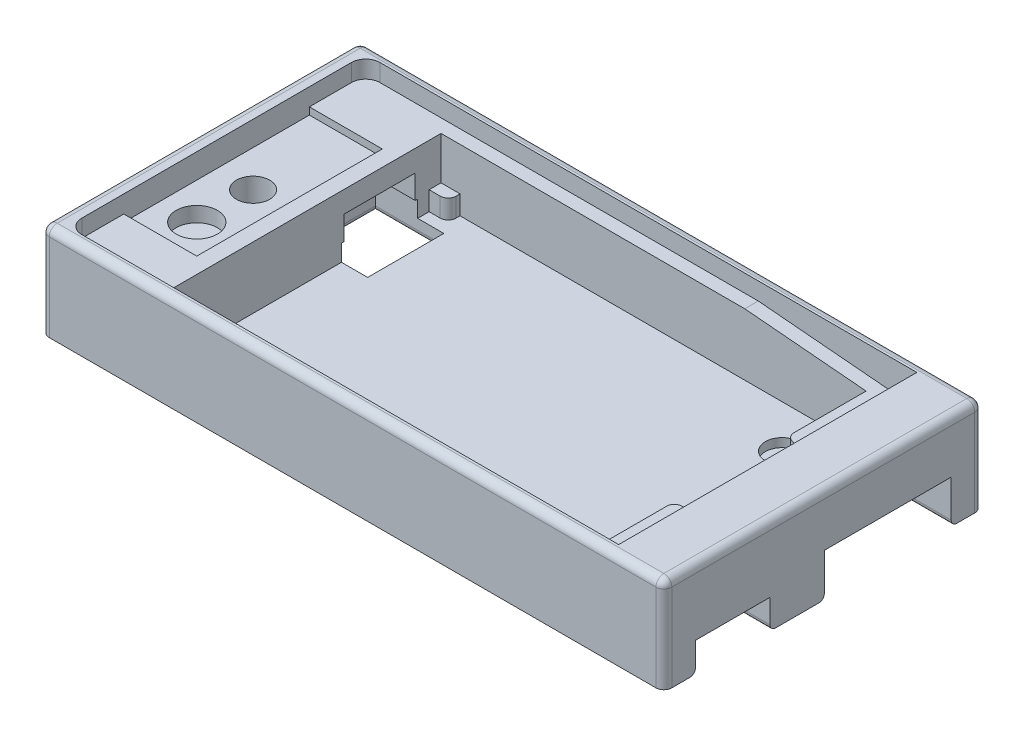
SolidWorks part; units mm, degrees
ref_plane "前视基准面" through (0, 0, 0) normal (0, 0, 1) x (1, 0, 0)
ref_plane "上视基准面" through (0, 0, 0) normal (0, 1, 0) x (1, 0, 0)
ref_plane "右视基准面" through (0, 0, 0) normal (1, 0, 0) x (0, 0, -1)
other "Configuration Table"
sketch "草图1" plane through (0, 0, 0) normal (0, 1, 0) x (1, 0, 0)
  line L0 (-39.25, 0) -> (39.25, 0) construction
  line L1 (-39.25, 20.1) -> (39.25, 20.1)
  line L2 (-39.25, 20.1) -> (-39.25, -20.1)
  line L3 (-39.25, -20.1) -> (39.25, -20.1)
  line L4 (39.25, 20.1) -> (39.25, -20.1)
  line L5 (-39.25, 20.1) -> (39.25, -20.1) construction
  line L6 (-39.25, -20.1) -> (39.25, 20.1) construction
  line L7 (-26.05, -17.1) -> (27.55, -17.1)
  line L8 (-26.05, -17.1) -> (-26.05, 17.1)
  line L9 (-26.05, 17.1) -> (27.55, 17.1)
  line L10 (27.55, -17.1) -> (27.55, 17.1)
  line L12 (32.25, 6.9973) -> (34.45, 6.9973)
  line L13 (32.25, 6.9973) -> (32.25, -6.9973)
  line L14 (32.25, -6.9973) -> (34.45, -6.9973)
  line L15 (34.45, 6.9973) -> (34.45, -6.9973)
  line L16 (-37.25, 18.8) -> (32.25, 18.8)
  line L17 (-37.25, 18.8) -> (-37.25, -18.8)
  line L18 (-37.25, -18.8) -> (32.25, -18.8)
  line L19 (32.25, 18.8) -> (32.25, -18.8)
  circle A0 centre (-32.65, 7.1) radius 2.6
  circle A1 centre (-32.65, 0) radius 2.1
  circle A2 centre (22.35, 11.6973) radius 2.1
  circle A3 centre (22.35, -11.6973) radius 2.1
  circle A4 centre (-32.65, -7.1) radius 2.6
  point P0 (0, 0)
  dimension "D1" = 4.2
  dimension "D6" = 5.2
  dimension "D2" = 5.2
  dimension "D3" = 5.4027
  dimension "D4" = 6.6
  dimension "D5" = 13
  dimension "D7" = 3
  dimension "D8" = 3
  dimension "D9" = 6.6
  dimension "D10" = 11.7
  dimension "D11" = 53.6
  dimension "D12" = 34.2
  dimension "D13" = 2.2
  dimension "D14" = 4.7
  dimension "D15" = 1.3
  dimension "D16" = 1.3
  dimension "D17" = 2
  dimension "D18" = 7
extrude "凸台-拉伸2" add sketch "草图1" along normal blind 2.2 contours L4 L1 L2 L3 L16 L19 L10 L12 L15 L14 L18 L17 | L15 L12 L10 L14 region at (0, 0, -19.2181) region at (33.35, 0, 0)
extrude "凸台-拉伸3" add sketch "草图1<4>" against normal blind 7.8 contours L19 L16 L17 L18 L7 L8 L9 A0 A1 A4 | L4 L1 L2 L3 L16 L19 L10 L12 L15 L14 L18 L17 | A4 | A0 | A1 | L15 L12 L13 L14 region at (0, 0, -19.2181) region at (33.35, 0, 0) region at (31.4598, 0, 0) region at (-32.65, 0, -7.1) region at (-32.65, 0, 0) region at (-32.65, 0, 7.1)
sketch "草图1<4>" plane through (0, 0, 0) normal (0, 1, 0) x (1, 0, 0) same geometry as "草图1"
sketch "草图2" plane through (0, 0, 0) normal (0, 1, 0) x (1, 0, 0)
  line L0 (-37.25, 18.8) -> (-37.25, -18.8) construction
  line L1 (-37.25, 11.7) -> (-28.05, 11.7)
  line L2 (-37.25, 11.7) -> (-37.25, -11.7)
  line L3 (-37.25, -11.7) -> (-28.05, -11.7)
  line L4 (-28.05, 11.7) -> (-28.05, -11.7)
  circle A0 centre (-32.65, 7.1) radius 2.6 construction
  circle A1 centre (-32.65, 7.1) radius 2.6 construction
  circle A2 centre (-32.65, -7.1) radius 2.6 construction
  circle A3 centre (-32.65, -7.1) radius 2.6 construction
  dimension "D1" = 4.6
  dimension "D2" = 4.6
  dimension "D3" = 4.6
extrude "切除-拉伸1" cut sketch "草图2" against normal blind 0.9
sketch "草图6" plane through (0, -0.9, 0) normal (0, 1, 0) x (1, 0, 0)
  circle A0 centre (-32.65, 7.1) radius 2.6 construction
  circle A1 centre (-32.65, 7.1) radius 2.6
  circle A2 centre (-32.65, -7.1) radius 2.6 construction
  circle A3 centre (-32.65, -7.1) radius 2.6
extrude "切除-拉伸2" cut sketch "草图6" against normal blind 1.9 contours A3 region at (-32.65, -0.9, 7.1)
sketch "草图7" plane through (0, -0.9, 0) normal (0, 1, 0) x (1, 0, 0)
  circle A0 centre (-32.65, 0) radius 2.1 construction
  circle A1 centre (-32.65, 0) radius 2.1
extrude "切除-拉伸3" cut sketch "草图7" against normal blind 1.1
sketch "草图8" plane through (0, -2, 0) normal (0, 1, 0) x (1, 0, 0)
  circle A0 centre (-32.65, 0) radius 1.2
  dimension "2.2" = 2.4
extrude "切除-拉伸4" cut sketch "草图8" against normal through all
sketch "草图9" plane through (0, -7.8, 0) normal (0, -1, 0) x (1, 0, 0)
  line L0 (39.25, -20.1) -> (39.25, 20.1) construction
  line L1 (-39.25, -20.1) -> (39.25, -20.1) construction
  line L2 (-39.25, -20.1) -> (-39.25, 20.1) construction
  line L3 (-39.25, 20.1) -> (39.25, 20.1) construction
  line L4 (39.25, -20.1) -> (39.25, 20.1)
  line L5 (-39.25, -20.1) -> (39.25, -20.1)
  line L6 (-39.25, -20.1) -> (-39.25, 20.1)
  line L7 (-39.25, 20.1) -> (39.25, 20.1)
extrude "凸台-拉伸4" add sketch "草图9" along normal blind 2
sketch "草图10" plane through (0, -7.8, 0) normal (0, 1, 0) x (1, 0, 0)
  circle A0 centre (22.35, -11.6973) radius 2.1 construction
  circle A1 centre (22.35, 11.6973) radius 2.1 construction
  circle A2 centre (22.35, -11.6973) radius 2.1
  circle A3 centre (22.35, 11.6973) radius 2.1
extrude "切除-拉伸5" cut sketch "草图10" against normal blind 1.1
sketch "草图11" plane through (0, -8.9, 0) normal (0, 1, 0) x (1, 0, 0)
  circle A0 centre (22.35, 11.6973) radius 1.2
  circle A1 centre (22.35, -11.6973) radius 1.2
  dimension "D1" = 2.4
  dimension "D2" = 2.4
extrude "切除-拉伸6" cut sketch "草图11" against normal through all
sketch "草图12" plane through (0, -9.8, 0) normal (0, -1, 0) x (1, 0, 0)
  line L0 (-26.05, -17.1) -> (27.55, -17.1) construction
  line L1 (-26.05, -17.1) -> (27.55, -17.1) construction
  line L7 (-30.8239, -4.85) -> (-26.3739, -4.85)
  line L8 (-30.8239, -4.85) -> (-30.8239, -13.85)
  line L9 (-30.8239, -13.85) -> (-26.3739, -13.85)
  line L10 (-26.3739, -4.85) -> (-26.3739, -13.85)
  line L11 (-30.8239, -4.85) -> (-26.3739, -13.85) construction
  line L12 (-30.8239, -13.85) -> (-26.3739, -4.85) construction
  line L13 (-28.5989, -9.35) -> (-23.0895, -9.35) construction
  line L14 (-31.3739, -4.55) -> (-26.3739, -4.55)
  line L15 (-31.3739, -4.55) -> (-31.3739, -14.15)
  line L16 (-31.3739, -14.15) -> (-26.3739, -14.15)
  line L17 (-26.3739, -4.55) -> (-26.3739, -14.15)
  point P6 (-28.5989, -9.35)
  dimension "D1" = 7.75
  dimension "D2" = 4.45
  dimension "D3" = 9
  dimension "D4" = 9.6
  dimension "D5" = 5
extrude "切除-拉伸7" cut sketch "草图12" against normal blind 7.1 contours L10 L7 L8 L9 region at (-28.5989, -9.8, -9.35)
extrude "切除-拉伸8" cut sketch "草图12<3>" against normal offset from surface (4.1 mm away) 3 contours L17 L14 L15 L16 L9 L8 L7 region at (-30.9321, -9.8, -9.35) up to face at (-28.5989, -2.7, -9.35)
sketch "草图12<3>" plane through (0, -9.8, 0) normal (0, -1, 0) x (1, 0, 0) same geometry as "草图12"
sketch "草图13" plane through (-26.3739, 0, 0) normal (-1, 0, 0) x (0, 0, 1)
  line L4 (-4.85, -2.7) -> (-13.85, -2.7)
  line L5 (-4.85, -2.7) -> (-13.85, -2.7)
  line L9 (-13.85, -2.7) -> (-13.85, -5.7)
  line L11 (-13.85, -5.7) -> (-14.15, -5.7)
  line L12 (-14.15, -9.8) -> (-4.55, -9.8)
  line L13 (-13.85, -5.7) -> (-14.15, -5.7)
  line L14 (-14.15, -5.7) -> (-14.15, -9.8)
  line L15 (-4.85, -5.7) -> (-4.85, -2.7)
  line L17 (-13.85, -2.7) -> (-13.85, -5.7)
  line L20 (-14.15, -9.8) -> (-4.55, -9.8)
  line L23 (-4.85, -5.7) -> (-4.85, -2.7)
  line L24 (-14.15, -5.7) -> (-14.15, -9.8)
  line L25 (-4.55, -9.8) -> (-4.55, -5.7)
  line L26 (-4.55, -9.8) -> (-4.55, -5.7)
  line L27 (-4.55, -5.7) -> (-4.85, -5.7)
  line L28 (-4.55, -5.7) -> (-4.85, -5.7)
  dimension "D1" = 0
extrude "切除-拉伸9" cut sketch "草图13" against normal up to surface (0.3239 mm away) up to face at (-26.05, -3.9, 0)
sketch "草图14" plane through (-26.05, 0, 0) normal (-1, 0, 0) x (0, 0, 1)
  line L4 (-14.15, -7.8) -> (-14.15, -9.8)
  line L5 (-14.15, -9.8) -> (-4.55, -9.8)
  line L7 (-4.55, -7.8) -> (-14.15, -7.8)
  line L9 (-14.15, -9.8) -> (-4.55, -9.8)
  line L11 (-4.55, -7.8) -> (-14.15, -7.8)
  line L12 (-14.15, -7.8) -> (-14.15, -9.8)
  line L14 (-4.55, -9.8) -> (-4.55, -7.8)
  line L15 (-4.55, -9.8) -> (-4.55, -7.8)
  dimension "D1" = 0
extrude "切除-拉伸10" cut sketch "草图14" against normal blind 3.3
fillet "圆角1" radius 1.8 4 edges at (32.25, 1.1, 18.8) (32.25, 1.1, -18.8) (-37.25, 1.1, -18.8) (-37.25, 1.1, 18.8)
fillet "圆角2" radius 1 8 edges at (39.25, -3.8, -20.1) (39.25, 2.2, 0) (39.25, -3.8, 20.1) (0, 2.2, -20.1) (-39.25, -3.8, -20.1) (0, 2.2, 20.1) (-39.25, 2.2, 0) (-39.25, -3.8, 20.1)
sketch "草图15" plane through (0, -7.8, 0) normal (0, 1, 0) x (1, 0, 0)
  line L0 (0, 0) -> (25.0264, 0) construction
  line L1 (-26.05, 17.1) -> (-23.65, 17.1)
  line L2 (-26.05, 17.1) -> (-26.05, 15.6)
  line L3 (-26.05, 15.6) -> (-23.65, 15.6)
  line L4 (-23.65, 17.1) -> (-23.65, 15.6)
  line L5 (-26.05, -15.6) -> (-23.65, -15.6)
  line L6 (-23.65, -17.1) -> (-23.65, -15.6)
  line L7 (-26.05, -17.1) -> (-23.65, -17.1)
  line L8 (-26.05, -17.1) -> (-26.05, -15.6)
  dimension "D1" = 2.4
  dimension "D2" = 1.5
extrude "凸台-拉伸5" add sketch "草图15" along normal blind 2.4
sketch "草图16" plane through (0, 0, 0) normal (0, 1, 0) x (1, 0, 0)
  line L0 (0, 0) -> (31.9375, 0) construction
  line L1 (27.55, -17.1) -> (27.55, 17.1) construction
  line L3 (30.2966, 8) -> (30.2966, -8)
  line L4 (32.25, 17) -> (32.25, -17) construction
  line L6 (30.2966, 10.6432) -> (30.2966, 8)
  line L7 (30.2966, -10.6432) -> (30.2966, -8)
  arc A0 (29.8157, 7.1059) -> (30.2966, 10.6432) centre (31.3306, 8.7013) cw
  arc A1 (29.8157, -7.1059) -> (30.2966, -10.6432) centre (31.3306, -8.7013) ccw
  ellipse E0 centre (27.55, 0) end of major axis (27.55, -8.1106) minor radius 4.7 (29.8157, -7.1059) -> (29.8157, 7.1059) ccw
  dimension "D1" = 2.2
revolve "切除-旋转1" [suppressed] cut sketch "草图16" angle 360 about L3
sketch "草图17" plane through (0, -7.8, 0) normal (0, 1, 0) x (1, 0, 0)
  circle A1 centre (-32.65, 0) radius 1.2
  circle A2 centre (-32.65, 0) radius 1.2
  dimension "D1" = 0
extrude "切除-拉伸11" cut sketch "草图17" against normal through all
sketch "草图19" plane through (0, 0, 20.1) normal (0, 0, 1) x (1, 0, 0)
  line L0 (12.25, 0) -> (34.1406, 0.2) construction
  line L1 (32.25, 2.2) -> (30.45, 2.2) construction
  line L2 (12.25, 0) -> (32.25, 2) construction
  line L6 (12.25, 0) -> (12.25, 2)
  line L11 (12.25, 0) -> (34.05, -2) construction
  line L12 (12.25, 0) -> (32.2733, -1.7518)
  line L13 (12.25, 0) -> (33.7215, -4.2678) construction
  line L14 (32.25, 2) -> (32.25, 0) construction
  line L15 (32.25, 0) -> (30.25, 0) construction
  line L17 (12.25, 2) -> (12.25, 3)
  line L18 (12.25, 3) -> (32.25, 3)
  line L19 (32.25, 2) -> (32.25, 3)
  line L20 (32.25, 2.2) -> (30.45, 2.2) construction
  line L21 (-35.45, 0) -> (30.45, 0) construction
  line L22 (-35.45, 0) -> (30.25, 0) construction
  line L23 (12.25, 2) -> (32.25, 2) construction
  line L24 (34.1416, 0) -> (32.3498, 0) construction
  line L25 (30.25, 0) -> (34.05, 0) construction
  line L26 (30.25, 0) -> (30.25, -2) construction
  line L27 (30.25, -2) -> (34.05, -2) construction
  line L28 (34.05, 0) -> (34.05, -2) construction
  line L29 (33.7215, -4.2678) -> (25.7215, -2.6777)
  line L30 (25.7215, -2.6777) -> (25.8517, -1.19)
  line L31 (34.1406, 0.2) -> (32.3489, 0.1836)
  circle A0 centre (12.25, 0) radius 20.0998 construction
  arc A3 (32.25, 2) -> (32.2733, -1.7518) centre (12.25, 0) cw
  circle A4 centre (12.25, 0) radius 21.8916 construction
  arc A5 (33.7215, -4.2678) -> (34.1406, 0.2) centre (12.25, 0) ccw
  line M8 (38.25, 1.2) -> (-38.25, 1.2)
  dimension "D1" = 2
  dimension "D2" = 20
  dimension "D3" = 5
  dimension "D4" = 2
  dimension "D5" = 20
  dimension "D6" = 6
  dimension "D7" = 1
  dimension "D8" = 1.8
  dimension "D9" = 2
  dimension "D10" = 8
  dimension "D11" = 0.2
extrude "切除-拉伸12" cut sketch "草图19" against normal up to surface (38.9 mm away) from surface contours L6 L12 M8 | L6 M8 region at (23.7042, 0.0997, 20.1) region at (22.2577, 2.0995, 20.1) up to face at (-2.5, 1.1, -18.8) starting at face at (-2.5, 1.1, 18.8)
extrude "切除-拉伸13" cut sketch "草图19<3>" against normal up to vertex (27.0973 mm away) from vertex contours L27 L12 L13 region at (30.7321, -2.2329, 20.1) up to point (34.45, 0, -6.9973) starting at point (34.45, 0, 6.9973)
sketch "草图19<3>" plane through (0, 0, 20.1) normal (0, 0, 1) x (1, 0, 0) same geometry as "草图19"
sketch "草图20" plane through (0.3556, 2.3642, 0) normal (0.195, 0.9808, 0) x (0.9808, -0.195, 0)
  line L0 (0.1121, 0) -> (27.7263, 0) construction
  line L1 (27.7263, 6.9973) -> (27.7263, -6.9973) construction
  line L2 (27.7263, 6.9973) -> (27.7263, -6.9973) construction
  line L3 (27.7263, 5.3609) -> (27.7263, -5.3609)
  line L4 (27.7263, 0) -> (31.3144, 0) construction
  line L5 (31.3144, 18.8) -> (31.3144, -18.8) construction
  line L6 (29.3869, 4.2263) -> (27.7263, 5.3609) construction
  line L9 (27.7263, -5.3609) -> (27.7263, 5.3609) construction
  ellipse E0 centre (27.7263, 0) end of major axis (27.7263, 5.3609) minor radius 3.5881 (27.7263, 5.3609) -> (27.7263, -5.3609) cw
revolve "切除-旋转2" [suppressed] cut sketch "草图20" angle 360 about L3
fillet "圆角4" [suppressed] radius 1
fillet "圆角5" radius 1 2 edges at (-23.65, -6.6, 15.6) (-23.65, -6.6, -15.6)
sketch "草图21" plane through (0, -2, 0) normal (0, 1, 0) x (1, 0, 0)
  circle A1 centre (-32.65, 0) radius 2.1
  circle A2 centre (-32.65, 0) radius 2.1
  dimension "D1" = 0
extrude "切除-拉伸14" cut sketch "草图21" against normal up to surface (6.9 mm away) up to face at (22.35, -8.9, -10.4973)
sketch "草图22" plane through (0, -9.8, 0) normal (0, -1, 0) x (1, 0, 0)
  line L0 (0, 0) -> (39.25, 0) construction
  line L2 (-39.25, 14.6675) -> (-39.25, 5.2675)
  line L3 (31.35, 16.1208) -> (39.25, 16.1208)
  line L4 (31.35, 16.1208) -> (31.35, 6.7208)
  line L5 (31.35, 6.7208) -> (39.25, 6.7208)
  line L6 (39.25, 16.1208) -> (39.25, 6.7208)
  line L7 (31.35, 16.1208) -> (39.25, 6.7208) construction
  line L8 (31.35, 6.7208) -> (39.25, 16.1208) construction
  line L9 (-39.25, 14.6675) -> (-31.35, 14.6675)
  line L10 (-39.25, 5.2675) -> (-31.35, 5.2675)
  line L11 (-31.35, 14.6675) -> (-31.35, 5.2675)
  line L13 (39.25, -19.1) -> (39.25, 19.1) construction
  line L14 (-39.25, 19.1) -> (-39.25, -19.1) construction
  point P5 (35.3, 11.4208)
  dimension "D1" = 7.9
  dimension "D2" = 9.4
extrude "切除-拉伸15" cut sketch "草图22" against normal blind 3.7
sketch "草图23" plane through (0, -9.8, 0) normal (0, -1, 0) x (1, 0, 0)
  line L1 (39.25, -16.1357) -> (30.85, -16.1357)
  line L2 (39.25, -16.1357) -> (39.25, -0.1357)
  line L3 (39.25, -0.1357) -> (30.85, -0.1357)
  line L4 (30.85, -16.1357) -> (30.85, -0.1357)
  line L6 (32.2733, -18.8) -> (12.25, -18.8) construction
  line L7 (32.2733, -18.8) -> (12.25, -18.8) construction
  line L8 (39.25, -19.1) -> (39.25, 6.7208) construction
  line L9 (39.25, -19.1) -> (39.25, 6.7208) construction
  dimension "D1" = 8.4
  dimension "D2" = 16
extrude "切除-拉伸16" cut sketch "草图23" against normal blind 5.4
fillet "圆角6" radius 0.7 13 edges at (-35.3, -9.8, 5.2675) (35.05, -9.8, -16.1357) (30.85, -9.8, -8.1357) (35.05, -9.8, -0.1357) (35.3, -9.8, 6.7208) (35.3, -9.8, 16.1208) (31.35, -9.8, 11.4208) (-22.75, -9.8, -9.35) (-27.0619, -9.8, -14.15) (-31.3739, -9.8, -9.35) (-27.0619, -9.8, -4.55) (-31.35, -9.8, 9.9675) (-35.3, -9.8, 14.6675)
fillet "圆角7" radius 1 3 edges at (27.55, -2.1898, 6.9973) (27.55, -2.1898, -6.9973) (27.55, -3.0411, 0)
